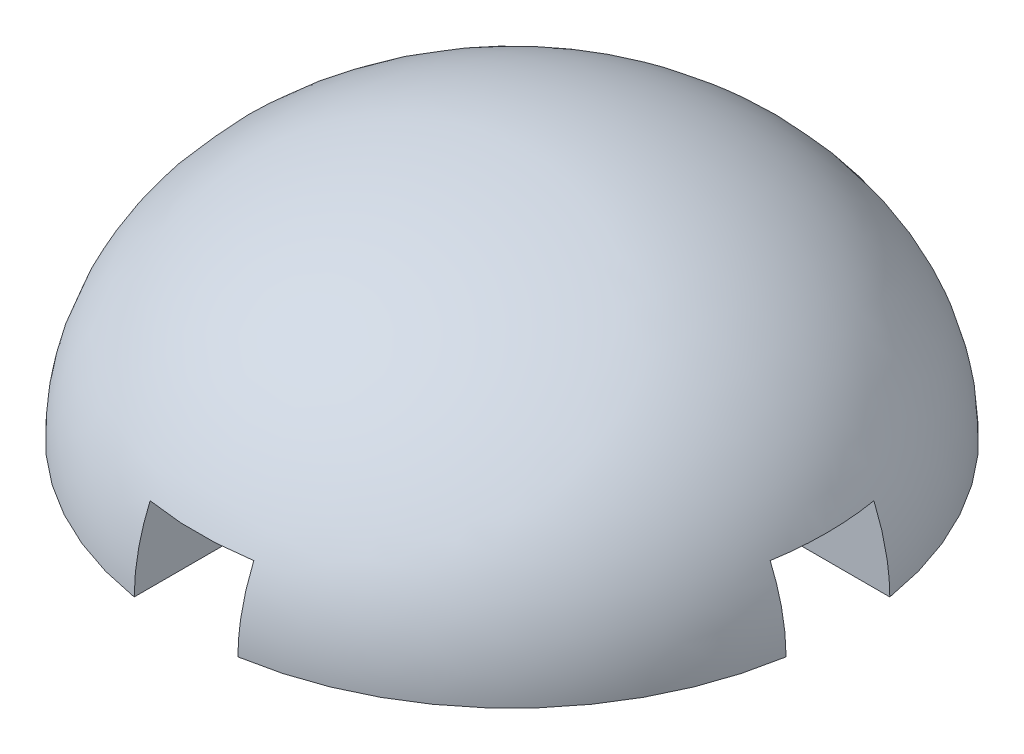
SolidWorks part; units mm, degrees
ref_plane "Front Plane" through (0, 0, 0) normal (0, 0, 1) x (1, 0, 0)
ref_plane "Top Plane" through (0, 0, 0) normal (0, 1, 0) x (1, 0, 0)
ref_plane "Right Plane" through (0, 0, 0) normal (1, 0, 0) x (0, 0, -1)
sketch "Sketch2" plane through (0, 0, 0) normal (0, 0, 1) x (1, 0, 0)
  line L0 (0, 0) -> (0, 17.5)
  line L2 (17.5, 0) -> (0, 0)
  arc A0 (17.5, 0) -> (0, 17.5) centre (0, 0) ccw
  dimension "D1" = 35
revolve "Revolve1" add sketch "Sketch2" angle 360 about L0
scale "Scale1" scale about centroid uniform scaling no x scale factor 1 y scale factor 0.75 z scale factor 1
ref_axis "Axis1" through (0, 0.9844, 0) along (0, 1, 0)
sketch "Sketch3" plane through (0, 0, 0) normal (0, 0, 1) x (1, 0, 0)
  line L3 (-2.75, 5.6406) -> (-2.75, 1.6406)
  line L9 (-2.75, 5.6406) -> (2.75, 5.6406)
  line L18 (-17.5, 1.6406) -> (17.5, 1.6406) construction
  line L19 (2.75, 1.6406) -> (2.75, 5.6406)
  line L20 (2.75, 1.6406) -> (-2.75, 1.6406)
  point P5 (-3.3894, 1.4063)
  point P9 (0.2443, 1.4063)
  point P11 (0, 5.4063)
  point P12 (0.2443, 1.4063)
  point P14 (0, 5.4063)
  dimension "D1" = 5.5
  dimension "D2" = 4
extrude "Cut-Extrude1" cut sketch "Sketch3" along normal mid plane 35
pattern_circular "CirPattern1" count 2 every 90 about axis through (0, 0.9844, 0) along (0, 1, 0) of "Cut-Extrude1"
sketch "Sketch4" plane through (0, 5.6406, 0) normal (0, -1, 0) x (1, 0, 0)
  circle A0 centre (0, 0) radius 2.5
  circle A1 centre (0, 0) radius 1.05
  dimension "D1" = 5
  dimension "D2" = 2.1
extrude "Boss-Extrude1" add sketch "Sketch4" along normal up to surface (4 mm away) up to face at (8.3802, 1.6406, 8.3802)
sketch "Sketch5" plane through (0, 5.6406, 0) normal (0, -1, 0) x (1, 0, 0)
  circle A0 centre (0, 0) radius 1.05
extrude "Cut-Extrude2" cut sketch "Sketch5" against normal blind 8
